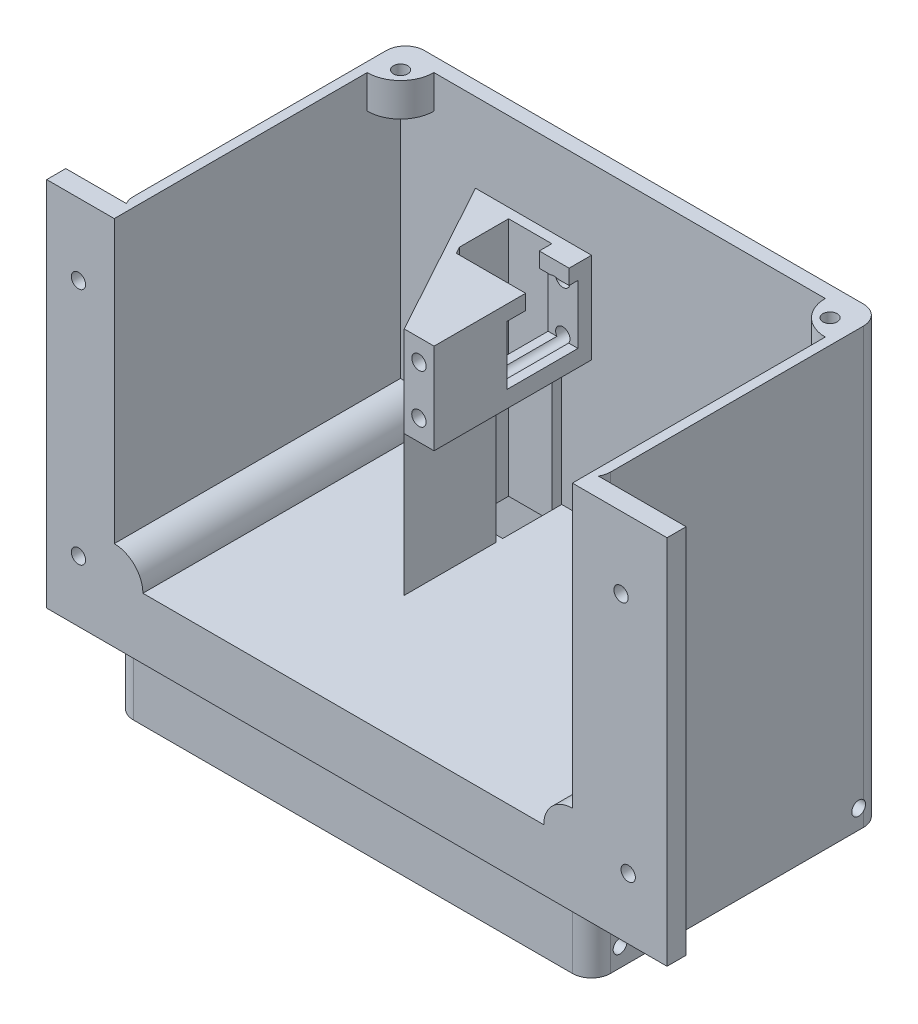
SolidWorks part; units mm, degrees
ref_plane "Front Plane" through (0, 0, 0) normal (0, 0, 1) x (1, 0, 0)
ref_plane "Top Plane" through (0, 0, 0) normal (0, 1, 0) x (1, 0, 0)
ref_plane "Right Plane" through (0, 0, 0) normal (1, 0, 0) x (0, 0, -1)
sketch "Sketch1" plane through (0, 0, 0) normal (0, 0, 1) x (1, 0, 0)
  line L0 (-47.6718, 33.255) -> (-47.6718, 35.255)
  line L1 (-49.6674, 35.255) -> (-47.6718, 35.255)
  line L2 (-49.6674, 35.255) -> (-49.6674, -64.745)
  line L3 (-49.6674, -64.745) -> (50.3326, -64.745)
  line L4 (50.3326, 35.255) -> (50.3326, -64.745)
  line L6 (-47.6718, 33.255) -> (-47.6718, -62.745)
  line L7 (-47.6718, -62.745) -> (48.3326, -62.745)
  line L8 (48.3326, 33.255) -> (48.3326, -62.745)
  line L9 (48.3326, 33.255) -> (48.3326, 35.255)
  line L10 (48.3326, 35.255) -> (50.3326, 35.255)
  dimension "D1" = 100
  dimension "D2" = 100
  dimension "D3" = 1.9956
  dimension "D4" = 2
  dimension "D6" = 2
extrude "Boss-Extrude1" add sketch "Sketch1" along normal blind 70
sketch "Sketch2" plane through (0, 0, 0) normal (0, 0, -1) x (-1, 0, 0)
  line L1 (-50.3326, 35.255) -> (49.6674, 35.255)
  line L2 (-50.3326, 35.255) -> (-50.3326, -64.745)
  line L3 (-50.3326, -64.745) -> (49.6674, -64.745)
  line L4 (49.6674, 35.255) -> (49.6674, -64.745)
extrude "Boss-Extrude2" add sketch "Sketch2" along normal blind 2 contours L1 L4 L3 L2
sketch "Sketch3" plane through (0, 0, 0) normal (0, 0, 1) x (1, 0, 0)
  line L0 (33.9342, -14.383) -> (33.9342, -33.383)
  line L1 (-7.6527, -14.383) -> (-13.9025, -14.383)
  line L3 (-7.6527, -33.383) -> (-13.9025, -33.383)
  line L4 (-13.9025, -14.383) -> (-13.9025, -33.383)
  line L5 (33.9342, -14.383) -> (40.1899, -14.383)
  line L7 (33.9342, -33.383) -> (40.1899, -33.383)
  line L8 (40.1899, -14.383) -> (40.1899, -33.383)
  line L9 (-7.6527, -14.383) -> (-7.6527, -33.383)
  circle A0 centre (37.1695, -19.0297) radius 1.5
  circle A1 centre (37.1899, -28.9161) radius 1.5
  circle A2 centre (-10.8058, -18.883) radius 1.5
  circle A3 centre (-10.8305, -29.0297) radius 1.5
extrude "Boss-Extrude4" add sketch "Sketch3" along normal blind 33
sketch "Sketch4" plane through (33.9342, 0, 0) normal (-1, 0, 0) x (0, 0, 1)
  line L0 (33, -33.383) -> (0, -33.383) construction
  line L1 (17.7261, -17.5315) -> (2.8469, -17.5315)
  line L2 (17.7261, -17.5315) -> (17.7261, -29.883)
  line L3 (17.7261, -29.883) -> (2.8469, -29.883)
  line L4 (2.8469, -17.5315) -> (2.8469, -29.883)
  dimension "D1" = 3.5
extrude "Cut-Extrude2" cut sketch "Sketch4" against normal blind 10 and the other way blind 49
sketch "Sketch5" plane through (0, 0, 70) normal (0, 0, 1) x (1, 0, 0)
  line L0 (-47.6718, -62.745) -> (-47.6718, 35.255) construction
  line L1 (48.3326, -62.745) -> (-47.6718, -62.745)
  line L2 (48.3326, -62.745) -> (48.3326, -19.0519)
  line L3 (48.3326, -19.0519) -> (-47.6718, -19.0519)
  line L4 (-47.6718, -62.745) -> (-47.6718, -19.0519)
extrude "Boss-Extrude5" add sketch "Sketch5" against normal blind 2
sketch "Sketch8" plane through (0, 35.255, 0) normal (0, 1, 0) x (1, 0, 0)
  line L1 (-47.6718, 0) -> (-40.6718, 0)
  line L2 (48.3326, 0) -> (48.3326, -7)
  line L5 (-47.6718, -7) -> (-47.6718, 0)
  line L6 (41.3326, 0) -> (48.3326, 0)
  arc A0 (-47.6718, -7) -> (-40.6718, 0) centre (-47.6718, 0) ccw
  arc A1 (41.3326, 0) -> (48.3326, -7) centre (48.3326, 0) ccw
  circle A5 centre (45.3326, -3) radius 1.5
  circle A6 centre (-44.6718, -3) radius 1.5
  dimension "D1" = 3
  dimension "D2" = 3
  dimension "D7" = 3
  dimension "D8" = 3
ref_plane "Plane1" through (0, 0, -2) normal (0, 0, -1) x (-1, 0, 0)
ref_plane "Plane2" through (0, 0, 58) normal (0, 0, -1) x (-1, 0, 0)
sketch "Sketch9" plane through (0, 0, 58) normal (0, 0, -1) x (-1, 0, 0)
  line L1 (-50.3326, 35.255) -> (49.6674, 35.255)
  line L2 (-50.3326, 35.255) -> (-50.3326, -64.745)
  line L3 (-50.3326, -64.745) -> (49.6674, -64.745)
  line L4 (49.6674, 35.255) -> (49.6674, -64.745)
extrude "Cut-Extrude3" cut sketch "Sketch9" against normal blind 42 contours L2 L3 L4 L1
sketch "Sketch10" plane through (0, 0, 58) normal (0, 0, 1) x (1, 0, 0)
  line L0 (50.3326, 35.255) -> (50.3326, -64.745) construction
  line L1 (-49.6674, -64.745) -> (50.3326, -64.745)
  line L2 (-49.6674, -64.745) -> (-49.6674, -23.5151)
  line L3 (-49.6674, -23.5151) -> (-15.7694, -23.5151)
  line L4 (50.3326, -64.745) -> (50.3326, -23.5151)
  line L8 (16.0922, -23.5151) -> (50.3326, -23.5151)
  line L9 (-10.9579, -23.5151) -> (-15.7694, -23.5151)
  line L10 (16.0922, -23.5151) -> (13.1563, -23.5151)
  line L12 (-10.9579, -23.5151) -> (-6.8172, -23.5151)
  arc A2 (-6.8172, -23.5151) -> (13.1563, -23.5151) centre (3.1695, -24.0297) ccw
extrude "Boss-Extrude7" add sketch "Sketch8" against normal blind 40
ref_plane "Plane3" through (0, 0, 58) normal (0, 0, 1) x (1, 0, 0)
sketch "Sketch15" plane through (0, 35.255, 0) normal (0, 1, 0) x (1, 0, 0)
  line L8 (-47.6718, -58) -> (-47.6718, -7)
  line L9 (-40.6718, 0) -> (41.3326, 0)
  line L10 (48.3326, -7) -> (48.3326, -58)
  line L11 (48.3326, -58) -> (50.3326, -58)
  line L12 (50.3326, -58) -> (50.3326, 2)
  line L13 (50.3326, 2) -> (-49.6674, 2)
  line L14 (-49.6674, 2) -> (-49.6674, -58)
  line L15 (-49.6674, -58) -> (-47.6718, -58)
  line L16 (-47.6718, -58) -> (-47.6718, -7)
  line L17 (-40.6718, 0) -> (41.3326, 0)
  line L18 (48.3326, -7) -> (48.3326, -58)
  line L19 (48.3326, -58) -> (50.3326, -58)
  line L20 (50.3326, -58) -> (50.3326, 2)
  line L21 (50.3326, 2) -> (-49.6674, 2)
  line L22 (-49.6674, 2) -> (-49.6674, -58)
  line L23 (-49.6674, -58) -> (-47.6718, -58)
  arc A2 (-47.6718, -7) -> (-40.6718, 0) centre (-47.6718, 0) ccw
  arc A3 (41.3326, 0) -> (48.3326, -7) centre (48.3326, 0) ccw
  arc A4 (-47.6718, -7) -> (-40.6718, 0) centre (-47.6718, 0) ccw
  arc A5 (41.3326, 0) -> (48.3326, -7) centre (48.3326, 0) ccw
  dimension "D1" = 0
extrude "Cut-Extrude5" cut sketch "Sketch15" against normal blind 3
sketch "Sketch17" plane through (0, 32.255, 0) normal (0, 1, 0) x (1, 0, 0)
  line L8 (-49.6674, -58) -> (-47.6718, -58)
  line L9 (-47.6718, -58) -> (-47.6718, -7)
  line L10 (-40.6718, 0) -> (41.3326, 0)
  line L11 (48.3326, -7) -> (48.3326, -58)
  line L12 (48.3326, -58) -> (50.3326, -58)
  line L13 (50.3326, -58) -> (50.3326, 2)
  line L14 (50.3326, 2) -> (-49.6674, 2)
  line L15 (-49.6674, 2) -> (-49.6674, -58)
  line L16 (-49.6674, -58) -> (-47.6718, -58)
  line L17 (-47.6718, -58) -> (-47.6718, -7)
  line L18 (-40.6718, 0) -> (41.3326, 0)
  line L19 (48.3326, -7) -> (48.3326, -58)
  line L20 (48.3326, -58) -> (50.3326, -58)
  line L21 (50.3326, -58) -> (50.3326, 2)
  line L22 (50.3326, 2) -> (-49.6674, 2)
  line L23 (-49.6674, 2) -> (-49.6674, -58)
  arc A2 (-47.6718, -7) -> (-40.6718, 0) centre (-47.6718, 0) ccw
  arc A3 (41.3326, 0) -> (48.3326, -7) centre (48.3326, 0) ccw
  arc A4 (-47.6718, -7) -> (-40.6718, 0) centre (-47.6718, 0) ccw
  arc A5 (41.3326, 0) -> (48.3326, -7) centre (48.3326, 0) ccw
  dimension "D1" = 0
extrude "Cut-Extrude8" cut sketch "Sketch17" against normal blind 30
sketch "Sketch20" plane through (0, -14.383, 0) normal (0, 1, 0) x (1, 0, 0)
  line L0 (-13.9025, -33) -> (-31.9742, 0)
  line L2 (-13.9025, -33) -> (-13.9025, 0)
  line L3 (-13.9025, 0) -> (-31.9742, 0)
  line L5 (-16.311, -2.0713) -> (-28.6827, -2.0713)
  line L6 (-28.6827, -2.0713) -> (-17.7393, -21.7736)
  line L8 (-16.311, -2.0713) -> (-13.9025, -2.0713)
  line L9 (-17.7393, -21.7736) -> (-13.9025, -21.7736)
  line L10 (-13.9025, 0) -> (-13.9025, -33)
  line M4 (-13.9025, 0) -> (-13.9025, -33)
  dimension "D1" = 0.343
extrude "Boss-Extrude13" add sketch "Sketch20" against normal blind 49 contours L9 L6 L5 L8 L3 L0 M4 region at (-22.6084, -14.383, 16.3193)
sketch "Sketch22" plane through (0, -62.745, 0) normal (0, 1, 0) x (1, 0, 0)
  line L0 (-28.6827, -2.0713) -> (-17.7393, -21.7736) construction
  line L1 (-13.9025, -2.0713) -> (-22.9603, -2.0713)
  line L2 (-13.9025, -2.0713) -> (-13.9025, -12.3737)
  line L3 (-13.9025, -12.3737) -> (-22.9603, -12.3737)
  line L4 (-22.9603, -2.0713) -> (-22.9603, -12.3737)
extrude "Cut-Extrude9" cut sketch "Sketch22" against normal blind 49
sketch "Sketch23" plane through (0, -14.383, 0) normal (0, 1, 0) x (1, 0, 0)
  line L0 (-7.6527, -33) -> (-7.6527, 0) construction
  line L2 (-13.9025, -4.7015) -> (-13.9025, -13.81)
  line L3 (-13.9025, -13.81) -> (-7.6527, -13.81)
  line L4 (-7.6527, -4.7015) -> (-7.6527, -13.81)
  line L5 (-13.9025, -4.7015) -> (-7.6527, -4.7015)
extrude "Cut-Extrude10" cut sketch "Sketch23" against normal blind 6 contours L3 L4 L5 L2
sketch "Sketch24" plane through (0, -64.745, 0) normal (0, -1, 0) x (1, 0, 0)
  line L1 (-42.1674, 55.5) -> (42.8326, 55.5)
  line L2 (-47.1674, 50.5) -> (-47.1674, 5.5)
  line L3 (-42.1674, 0.5) -> (41.8995, 0.5)
  line L4 (50.3326, 58) -> (-49.6674, 58)
  line L5 (-49.6674, 58) -> (-49.6674, -2)
  line L6 (-49.6674, -2) -> (50.3326, -2)
  line L7 (50.3326, -2) -> (50.3326, 58)
  line L8 (50.3326, 58) -> (-49.6674, 58)
  line L9 (-49.6674, 58) -> (-49.6674, -2)
  line L10 (-49.6674, -2) -> (50.3326, -2)
  line L11 (50.3326, -2) -> (50.3326, 58)
  line L12 (47.8326, 50.5) -> (47.8326, 5.5)
  line L15 (-47.1674, 50.5) -> (-42.1674, 50.5)
  line L16 (-42.1674, 55.5) -> (-42.1674, 50.5)
  line L19 (47.8326, 50.5) -> (42.8326, 50.5)
  line L20 (42.8326, 55.5) -> (42.8326, 50.5)
  line L23 (-47.1674, 5.5) -> (-42.1674, 5.5)
  line L24 (-42.1674, 0.5) -> (-42.1674, 5.5)
  line L27 (47.8326, 5.5) -> (41.8995, 5.5)
  line L28 (41.8995, 0.5) -> (41.8995, 5.5)
  dimension "D2" = 2.5
  dimension "D3" = 2.5
  dimension "D4" = 2.5
  dimension "D5" = 2.5
  dimension "D6" = 5
  dimension "D7" = 5
  dimension "D8" = 5
  dimension "D9" = 5
  dimension "D10" = 5
  dimension "D1" = 0
extrude "Boss-Extrude14" add sketch "Sketch24" along normal blind 24
sketch "Sketch25" plane through (0, 0, 58) normal (0, 0, 1) x (1, 0, 0)
  line L0 (-49.6674, -75.5297) -> (50.3326, -75.5297)
  line L8 (50.3326, -88.745) -> (50.3326, 2.255)
  line L9 (50.3326, 2.255) -> (48.3326, 2.255)
  line L10 (48.3326, 2.255) -> (48.3326, -62.745)
  line L11 (48.3326, -62.745) -> (-47.6718, -62.745)
  line L12 (-47.6718, -62.745) -> (-47.6718, 2.255)
  line L13 (-47.6718, 2.255) -> (-49.6674, 2.255)
  line L14 (-49.6674, 2.255) -> (-49.6674, -88.745)
  line L15 (-49.6674, -88.745) -> (50.3326, -88.745)
  line L16 (50.3326, -75.5297) -> (50.3326, 2.255)
  line L17 (50.3326, 2.255) -> (48.3326, 2.255)
  line L18 (48.3326, 2.255) -> (48.3326, -62.745)
  line L19 (48.3326, -62.745) -> (-47.6718, -62.745)
  line L20 (-47.6718, -62.745) -> (-47.6718, 2.255)
  line L21 (-47.6718, 2.255) -> (-49.6674, 2.255)
  line L22 (-49.6674, 2.255) -> (-49.6674, -75.5297)
  dimension "D1" = 0
extrude "Boss-Extrude15" add sketch "Sketch25" along normal blind 10
sketch "Sketch26" plane through (0, 0, 68) normal (0, 0, 1) x (1, 0, 0)
  line L1 (-49.6674, 2.255) -> (50.3326, 2.255)
  line L2 (-49.6674, 2.255) -> (-49.6674, -75.5297)
  line L3 (-49.6674, -75.5297) -> (50.3326, -75.5297)
  line L4 (50.3326, 2.255) -> (50.3326, -75.5297)
  line L5 (-61.8305, -75.5297) -> (68.1695, -75.5297)
  line L6 (-61.8305, -75.5297) -> (-61.8305, 2.255)
  line L7 (-61.8305, 2.255) -> (68.1695, 2.255)
  line L8 (68.1695, -75.5297) -> (68.1695, 2.255)
  circle A0 centre (58.0613, -10.5297) radius 1.5
  circle A1 centre (58.0613, -60.5297) radius 1.5
  circle A2 centre (-55.0641, -10.5297) radius 1.5
  circle A3 centre (-55.0641, -60.5297) radius 1.5
  line M2 (50.3326, 2.255) -> (48.3326, 2.255)
  line M3 (48.3326, 2.255) -> (48.3326, -62.745)
  line M4 (48.3326, -62.745) -> (-47.6718, -62.745)
  line M5 (-47.6718, -62.745) -> (-47.6718, 2.255)
  line M6 (-47.6718, 2.255) -> (-49.6674, 2.255)
  line M7 (-49.6674, 2.255) -> (-49.6674, -75.5297)
  line M8 (-49.6674, -75.5297) -> (50.3326, -75.5297)
  line M9 (50.3326, -75.5297) -> (50.3326, 2.255)
  dimension "D1" = 50
  dimension "D2" = 15
extrude "Boss-Extrude16" add sketch "Sketch26" against normal blind 7 contours L7 L6 L5 A3 A2 M7 | L5 L8 L7 A1 A0 M9 region at (-55.7593, -36.6541, 68) region at (59.2633, -36.6487, 68)
sketch "Sketch27" plane through (0, 0, -2) normal (0, 0, -1) x (-1, 0, 0)
  line L1 (-50.3326, 2.255) -> (49.6674, 2.255)
  line L2 (-50.3326, 2.255) -> (-50.3326, -88.745)
  line L3 (-50.3326, -88.745) -> (49.6674, -88.745)
  line L4 (49.6674, 2.255) -> (49.6674, -88.745)
extrude "Boss-Extrude17" add sketch "Sketch27" along normal blind 1 contours L2 L3 L4 L1
extrude "Cut-Extrude11" cut sketch "Sketch26<3>" against normal blind 8 contours L7 L6 L5 A3 A2 M7 | L5 L8 L7 A1 A0 M9 | M9 M2 M3 M4 M5 M6 M7 M8 region at (-48.6696, 0.9881, 68) region at (-55.7593, -36.6541, 68) region at (59.2633, -36.6487, 68)
sketch "Sketch26<3>" plane through (0, 0, 68) normal (0, 0, 1) x (1, 0, 0) same geometry as "Sketch26"
sketch "Sketch28" plane through (0, -62.745, 0) normal (0, 1, 0) x (1, 0, 0)
  line L2 (-13.9025, -13.81) -> (-13.9025, -21.7736)
  line L3 (-13.9025, -21.7736) -> (-17.7393, -21.7736)
  line L5 (-22.9603, -12.3737) -> (-17.7393, -21.7736)
  line L6 (-22.9603, -2.0713) -> (-28.6827, -2.0713)
  line L7 (-28.6827, -2.0713) -> (-22.9603, -12.3737)
  line L8 (-22.9603, -2.0713) -> (-22.9603, -12.3737)
  line L9 (-13.9025, -13.81) -> (-22.1626, -13.81)
  line M6 (-13.9025, -12.3737) -> (-22.9603, -12.3737)
  line M7 (-22.9603, -12.3737) -> (-17.7393, -21.7736)
  line M8 (-17.7393, -21.7736) -> (-13.9025, -21.7736)
extrude "Boss-Extrude18" add sketch "Sketch28" along normal up to surface (48.362 mm away) contours L2 M6 M7 M8 | L8 L6 L7 region at (-24.8678, -62.745, 5.5054) region at (-17.0615, -62.745, 17.3065) up to face at (-14.8766, -14.383, 12.5594)
sketch "Sketch32" plane through (0, -14.383, 0) normal (0, 1, 0) x (1, 0, 0)
  line L0 (40.1899, -33) -> (33.9342, -33) construction
  line L1 (39.1067, -33) -> (48.3326, -33)
  line L2 (39.1067, -33) -> (39.1067, -15.897)
  line L3 (39.1067, -15.897) -> (48.3326, -15.897)
  line L4 (48.3326, -33) -> (48.3326, -15.897)
  line L5 (48.3326, -60) -> (48.3326, 0) construction
extrude "Boss-Extrude19" add sketch "Sketch32" against normal up to surface (48.362 mm away) contours L2 L3 L4 L1 up to face at (-12.1073, -62.745, 17.2866)
sketch "Sketch33" plane through (0, 0, 0) normal (0, 0, 1) x (1, 0, 0)
  line L10 (-47.6718, -62.745) -> (-41.6718, -62.745)
  line L11 (-47.6718, -62.745) -> (-47.6718, -56.745)
  line L14 (48.3326, -62.745) -> (42.3326, -62.745)
  line L15 (48.3326, -62.745) -> (48.3326, -56.745)
  arc A0 (48.3326, -56.745) -> (42.3326, -62.745) centre (48.3326, -62.745) ccw
  arc A1 (-41.6718, -62.745) -> (-47.6718, -56.745) centre (-47.6718, -62.745) ccw
extrude "Boss-Extrude20" add sketch "Sketch33" along normal up to surface (60 mm away) up to face at (0.3315, -33.4412, 60)
sketch "Sketch34" plane through (0, 0, 60) normal (0, 0, 1) x (1, 0, 0)
  line L1 (-61.8305, 2.255) -> (68.1695, 2.255)
  line L2 (-61.8305, 2.255) -> (-61.8305, -75.5297)
  line L3 (-61.8305, -75.5297) -> (68.1695, -75.5297)
  line L4 (68.1695, 2.255) -> (68.1695, -75.5297)
  line L5 (-49.6674, 2.255) -> (50.3326, 2.255)
  line L6 (-49.6674, 2.255) -> (-49.6674, -75.5297)
  line L7 (-49.6674, -75.5297) -> (50.3326, -75.5297)
  line L8 (50.3326, 2.255) -> (50.3326, -75.5297)
  circle A0 centre (-55.1762, -62.745) radius 1.5
  circle A1 centre (-55.1762, -12.745) radius 1.5
  circle A2 centre (58.5359, -12.745) radius 1.5
  circle A3 centre (60.0359, -62.745) radius 1.5
  line M4 (-49.6674, 2.255) -> (-49.6674, -75.5297)
  line M6 (50.3326, -75.5297) -> (50.3326, 2.255)
  dimension "D1" = 50
  dimension "D2" = 50
  dimension "D3" = 15
  dimension "D4" = 15
extrude "Boss-Extrude21" add sketch "Sketch34" against normal blind 4 contours L2 L3 L1 A1 A0 M4 | L4 L1 L3 A3 A2 M6 region at (-55.7576, -36.6205, 60) region at (59.2507, -36.6259, 60)
fillet "Fillet1" radius 4 4 edges at (-49.6674, -82.1373, 58) (50.3326, -82.1373, 58) (50.3326, -43.245, -3) (-49.6674, -43.245, -3)
sketch "Sketch38" plane through (-49.6674, 0, 0) normal (-1, 0, 0) x (0, 0, 1)
  circle A0 centre (2, -84.745) radius 1.45
  circle A1 centre (52, -84.745) radius 1.45
  dimension "D1" = 2.9
  dimension "D2" = 2.9
extrude "Cut-Extrude32" cut sketch "Sketch38" against normal blind 127
